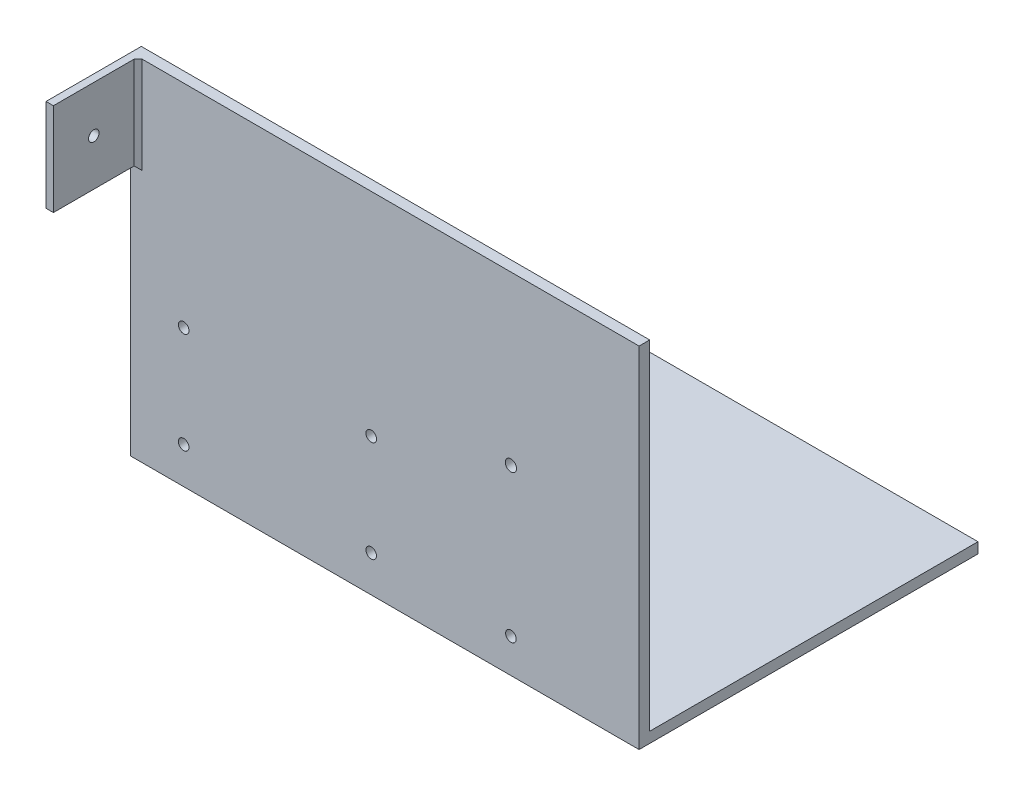
SolidWorks part; units mm, degrees
material "6061 Alloy"
ref_plane "Front Plane" through (0, 0, 0) normal (0, 0, 1) x (1, 0, 0)
ref_plane "Top Plane" through (0, 0, 0) normal (0, 1, 0) x (1, 0, 0)
ref_plane "Right Plane" through (0, 0, 0) normal (1, 0, 0) x (0, 0, -1)
sketch "Sketch1" plane through (0, 0, 0) normal (0, 1, 0) x (1, 0, 0)
  line L1 (152.4, 101.6) -> (-152.4, 101.6)
  line L2 (152.4, 101.6) -> (152.4, -101.6)
  line L3 (152.4, -101.6) -> (-152.4, -101.6)
  line L4 (-152.4, 101.6) -> (-152.4, -101.6)
  line L5 (152.4, 101.6) -> (-152.4, -101.6) construction
  line L6 (152.4, -101.6) -> (-152.4, 101.6) construction
  point P0 (0, 0)
  dimension "D1" = 304.8
  dimension "D2" = 203.2
extrude "Boss-Extrude1" add sketch "Sketch1" along normal blind 6.35
sketch "Sketch2" plane through (0, 6.35, 0) normal (0, 1, 0) x (1, 0, 0)
  line L0 (152.4, -101.6) -> (152.4, 101.6) construction
  line L6 (-152.4, -101.6) -> (152.4, -101.6)
  line L7 (-152.4, -101.6) -> (-152.4, -95.25)
  line L8 (-152.4, -95.25) -> (152.4, -95.25)
  line L9 (152.4, -101.6) -> (152.4, -95.25)
  dimension "D2" = 6.35
extrude "Boss-Extrude2" add sketch "Sketch2" along normal blind 40.64
sketch "Sketch3" plane through (152.4, 0, 0) normal (1, 0, 0) x (0, 0, -1)
  line L0 (0, 55) -> (0, -55) construction
  line L1 (-101.6, 46.99) -> (-81.1967, 46.99)
  line L2 (-101.6, 46.99) -> (-101.6, 6.35)
  line L3 (-101.6, 6.35) -> (-81.1967, 6.35)
  line L4 (-81.1967, 46.99) -> (-81.1967, 6.35)
  line L5 (101.6, 6.35) -> (81.1967, 6.35)
  line L6 (81.1967, 46.99) -> (81.1967, 6.35)
  line L7 (101.6, 46.99) -> (81.1967, 46.99)
  line L8 (101.6, 46.99) -> (101.6, 6.35)
extrude "Cut-Extrude1" cut sketch "Sketch3" against normal through all
extrude "Boss-Extrude3" add sketch "Sketch2<2>" along normal blind 203.2
sketch "Sketch2<2>" plane through (0, 6.35, 0) normal (0, 1, 0) x (1, 0, 0) same geometry as "Sketch2"
sketch "Sketch9" plane through (0, 0, 0) normal (0, -1, 0) x (1, 0, 0)
  circle A3 centre (-120.65, 79.0786) radius 3.175
  circle A4 centre (-120.65, 18.103) radius 3.175
  circle A7 centre (-8.205, 79.0786) radius 3.175
  circle A8 centre (-8.205, 18.103) radius 3.175
  circle A10 centre (75.5479, 73.6275) radius 3.175
extrude "Cut-Extrude2" cut sketch "Sketch9" against normal blind 10.922
sketch "Sketch10" plane through (0, 0, 101.6) normal (0, 0, 1) x (1, 0, 0)
  circle A4 centre (-120.65, 82.55) radius 3.175
  circle A5 centre (-120.65, 21.8994) radius 3.175
  circle A8 centre (-8.205, 82.4646) radius 3.175
  circle A9 centre (-8.205, 21.8141) radius 3.175
  circle A12 centre (75.5479, 109.1387) radius 3.3928
  circle A13 centre (75.5479, 20.4703) radius 3.175
extrude "Cut-Extrude3" cut sketch "Sketch10" against normal blind 10.922
sketch "Sketch11" plane through (0, 0, 101.6) normal (0, 0, 1) x (1, 0, 0)
  line L1 (-152.4, 209.55) -> (-147.9592, 209.55)
  line L2 (-152.4, 209.55) -> (-152.4, 154.0645)
  line L3 (-152.4, 154.0645) -> (-147.9592, 154.0645)
  line L4 (-147.9592, 209.55) -> (-147.9592, 154.0645)
extrude "Boss-Extrude7" add sketch "Sketch11" along normal blind 50.8
chamfer "Chamfer1" distance 2.38 angle 45 2 edges at (-147.9592, 181.8073, 101.6) (-150.1796, 154.0645, 101.6)
sketch "Sketch12" plane through (0, 0, 0) normal (0, -1, 0) x (1, 0, 0)
  line L1 (-152.4, -101.6) -> (-147.3104, -101.6)
  line L2 (-152.4, -101.6) -> (-152.4, -50.3982)
  line L3 (-152.4, -50.3982) -> (-147.3104, -50.3982)
  line L4 (-147.3104, -101.6) -> (-147.3104, -50.3982)
extrude "Boss-Extrude8" add sketch "Sketch12" along normal blind 50.8
chamfer "Chamfer2" distance 2.38 angle 45 2 edges at (-149.8552, 0, -50.3982) (-147.3104, 0, -75.9991)
sketch "Sketch13" plane through (-147.3104, 0, 0) normal (1, 0, 0) x (0, 0, -1)
  circle A0 centre (75.9991, -26.59) radius 3.175
extrude "Cut-Extrude4" cut sketch "Sketch13" against normal blind 50.8
sketch "Sketch14" plane through (-147.9592, 0, 0) normal (1, 0, 0) x (0, 0, -1)
  circle A0 centre (-128.19, 181.8073) radius 3.175
extrude "Cut-Extrude5" cut sketch "Sketch14" against normal blind 50.8
